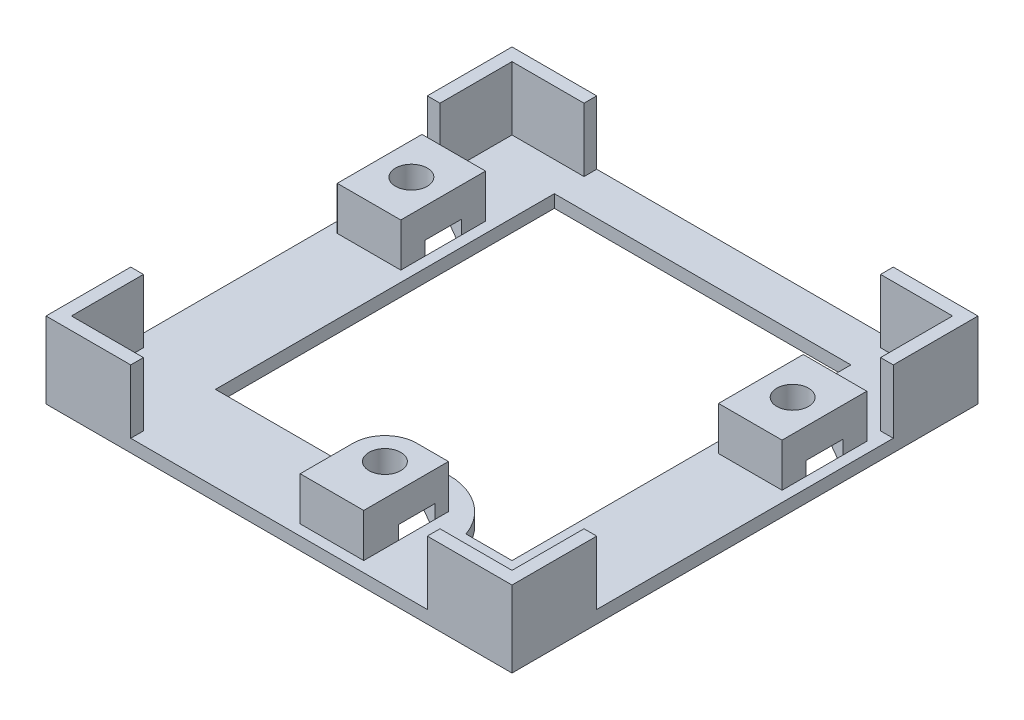
SolidWorks part; units mm, degrees
ref_plane "Front Plane" through (0, 0, 0) normal (0, 0, 1) x (1, 0, 0)
ref_plane "Top Plane" through (0, 0, 0) normal (0, 1, 0) x (1, 0, 0)
ref_plane "Right Plane" through (0, 0, 0) normal (1, 0, 0) x (0, 0, -1)
sketch "Sketch1" plane through (0, 0, 0) normal (0, 1, 0) x (1, 0, 0)
  line L0 (31.6569, 8) -> (36, 8)
  line L1 (0, 0) -> (44, 0)
  line L2 (0, 0) -> (0, 44)
  line L3 (0, 44) -> (44, 44)
  line L4 (44, 0) -> (44, 44)
  line L5 (1, 32.2321) -> (1, 28.7679)
  line L6 (1, 28.7679) -> (4, 27.0359)
  line L7 (4, 27.0359) -> (7, 28.7679)
  line L8 (7, 28.7679) -> (7, 32.2321)
  line L9 (7, 32.2321) -> (4, 33.9641)
  line L10 (4, 33.9641) -> (1, 32.2321)
  line L11 (37, 32.2321) -> (37, 28.7679)
  line L12 (37, 28.7679) -> (40, 27.0359)
  line L13 (40, 27.0359) -> (43, 28.7679)
  line L14 (43, 28.7679) -> (43, 32.2321)
  line L15 (43, 32.2321) -> (40, 33.9641)
  line L16 (40, 33.9641) -> (37, 32.2321)
  line L17 (23, 7.7321) -> (23, 4.2679)
  line L18 (23, 4.2679) -> (26, 2.5359)
  line L19 (26, 2.5359) -> (29, 4.2679)
  line L20 (29, 4.2679) -> (29, 7.7321)
  line L21 (29, 7.7321) -> (26, 9.4641)
  line L22 (26, 9.4641) -> (23, 7.7321)
  line L23 (8, 40) -> (36, 40)
  line L24 (8, 40) -> (8, 8)
  line L25 (8, 8) -> (20.3431, 8)
  line L26 (36, 40) -> (36, 8)
  circle A0 centre (4, 30.5) radius 1.5
  circle A1 centre (40, 30.5) radius 1.5
  circle A2 centre (26, 6) radius 1.5
  circle A3 centre (4, 30.5) radius 3 construction
  circle A4 centre (40, 30.5) radius 3 construction
  circle A5 centre (26, 6) radius 3 construction
  arc A6 (31.6569, 8) -> (20.3431, 8) centre (26, 6) ccw
  dimension "D3" = 3
  dimension "D16" = 12
  dimension "D1" = 44
  dimension "D2" = 44
  dimension "D4" = 36
  dimension "D5" = 24.5
  dimension "D6" = 14
  dimension "D7" = 6
  dimension "D8" = 6
  dimension "D9" = 6
  dimension "D10" = 4
  dimension "D11" = 6
  dimension "D12" = 8
  dimension "D13" = 8
  dimension "D14" = 4
  dimension "D15" = 8
extrude "Boss-Extrude1" add sketch "Sketch1" along normal blind 1.2 contours L1 L4 L3 L2 L22 L21 L20 L19 L18 L17 L16 L15 L14 L13 L12 L11 L10 L9 L8 L7 L6 L5 L0 A6 L25 L24 L23 L26 | L21 L22 L17 L18 L19 L20 A2 | L15 L16 L11 L12 L13 L14 A1 | L9 L10 L5 L6 L7 L8 A0 region at (0.6223, 0, -22) region at (2.5458, 0, -33.0187) region at (38.5458, 0, -33.0187) region at (24.5458, 0, -8.5187)
sketch "Sketch4" plane through (0, 1.2, 0) normal (0, 1, 0) x (1, 0, 0)
  line L1 (0, 44) -> (8, 44)
  line L2 (0, 44) -> (0, 42.8)
  line L3 (0, 42.8) -> (8, 42.8)
  line L4 (8, 44) -> (8, 42.8)
  line L5 (0, 42.8) -> (1.2, 42.8)
  line L6 (0, 42.8) -> (0, 36)
  line L7 (0, 36) -> (1.2, 36)
  line L8 (1.2, 42.8) -> (1.2, 36)
  line L9 (44, 44) -> (36, 44)
  line L10 (44, 44) -> (44, 42.8)
  line L11 (44, 42.8) -> (36, 42.8)
  line L12 (36, 44) -> (36, 42.8)
  line L13 (44, 42.8) -> (42.8, 42.8)
  line L14 (44, 42.8) -> (44, 36)
  line L15 (44, 36) -> (42.8, 36)
  line L16 (42.8, 42.8) -> (42.8, 36)
  line L17 (44, 0) -> (36, 0)
  line L18 (44, 0) -> (44, 1.2)
  line L19 (44, 1.2) -> (36, 1.2)
  line L20 (36, 0) -> (36, 1.2)
  line L21 (44, 1.2) -> (42.8, 1.2)
  line L22 (44, 1.2) -> (44, 8)
  line L23 (44, 8) -> (42.8, 8)
  line L24 (42.8, 1.2) -> (42.8, 8)
  line L25 (0, 0) -> (8, 0)
  line L26 (0, 0) -> (0, 1.2)
  line L27 (0, 1.2) -> (8, 1.2)
  line L28 (8, 0) -> (8, 1.2)
  line L29 (0, 1.2) -> (1.2, 1.2)
  line L30 (0, 1.2) -> (0, 8)
  line L31 (0, 8) -> (1.2, 8)
  line L32 (1.2, 1.2) -> (1.2, 8)
  line M31 (0, 0) -> (44, 0)
  line M32 (44, 0) -> (44, 44)
  line M33 (44, 44) -> (0, 44)
  line M34 (0, 44) -> (0, 0)
  dimension "D1" = 8
  dimension "8" = 8
  dimension "D3" = 8
  dimension "D4" = 8
  dimension "D5" = 1.2
  dimension "D6" = 1.2
  dimension "D7" = 1.2
  dimension "D8" = 1.2
  dimension "D9" = 8
  dimension "D10" = 8
  dimension "D11" = 8
  dimension "D12" = 8
extrude "Boss-Extrude4" add sketch "Sketch4" along normal blind 6 contours L4 L3 M33 M34 | L12 L11 M33 M32 | L11 L16 L15 M32 | L8 L3 L7 M34 | L27 L32 L31 M34 | L28 L27 M31 M34 | L24 L19 L23 M32 | L19 L20 L17 L18 region at (4, 1.2, -43.4) region at (0.6, 1.2, -39.4) region at (40, 1.2, -43.4) region at (0.6, 1.2, -4.6) region at (43.4, 1.2, -39.4) region at (4, 1.2, -0.6) region at (43.4, 1.2, -4.6)
sketch "Sketch5" plane through (0, 1.2, 0) normal (0, 1, 0) x (1, 0, 0)
  line L0 (0, 8) -> (0, 36) construction
  line L1 (1, 34.5) -> (7, 34.5)
  line L2 (1, 34.5) -> (1, 26.5)
  line L3 (1, 26.5) -> (7, 26.5)
  line L4 (7, 34.5) -> (7, 26.5)
  line L5 (37, 34.5) -> (43, 34.5)
  line L6 (37, 34.5) -> (37, 26.5)
  line L7 (37, 26.5) -> (43, 26.5)
  line L8 (43, 34.5) -> (43, 26.5)
  line L9 (26, 9) -> (29, 9)
  line L10 (23, 6) -> (23, 1)
  line L11 (23, 1) -> (29, 1)
  line L12 (29, 9) -> (29, 1)
  line L13 (44, 8) -> (44, 36) construction
  line L15 (8, 0) -> (36, 0) construction
  arc A0 (26, 9) -> (23, 6) centre (26, 6) ccw
  point P18 (40, 34.5)
  point P21 (0, 0)
  point P24 (23, 9)
  dimension "D11" = 3
  dimension "D1" = 6
  dimension "D2" = 6
  dimension "D3" = 8
  dimension "D4" = 8
  dimension "D5" = 1
  dimension "D6" = 1
  dimension "D7" = 8
  dimension "D8" = 14
  dimension "D9" = 6
  dimension "D10" = 1
  dimension "D12" = 28.5
extrude "Boss-Extrude8" add sketch "Sketch5" along normal blind 4.1
extrude "Cut-Extrude1" cut sketch "Sketch1<3>" along normal blind 2.5 contours L9 L10 L5 L6 L7 L8 A0 | L21 L22 L17 L18 L19 L20 A2 | L15 L16 L11 L12 L13 L14 A1 region at (2.5458, 0, -33.0187) region at (38.5458, 0, -33.0187) region at (24.5458, 0, -8.5187)
sketch "Sketch1<3>" plane through (0, 0, 0) normal (0, 1, 0) x (1, 0, 0) same geometry as "Sketch1"
extrude "Cut-Extrude2" cut sketch "Sketch1<4>" along normal through all contours A0 | A2 | A1 region at (4, 0, -30.5) region at (40, 0, -30.5) region at (26, 0, -6)
sketch "Sketch1<4>" plane through (0, 0, 0) normal (0, 1, 0) x (1, 0, 0) same geometry as "Sketch1"
